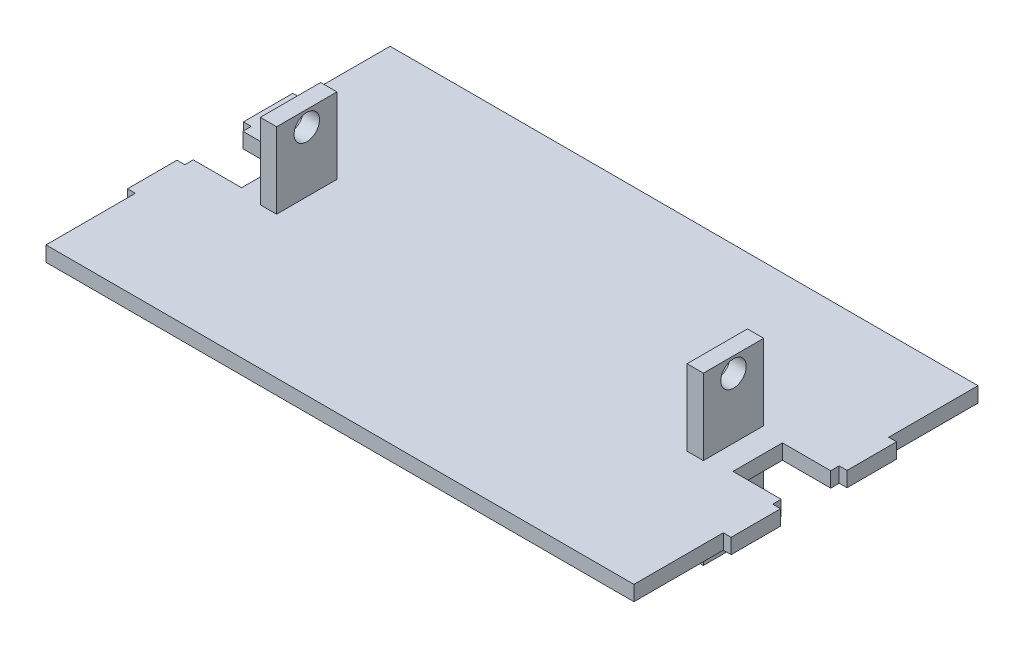
SolidWorks part; units mm, degrees
ref_plane "Front Plane" through (0, 0, 0) normal (0, 0, 1) x (1, 0, 0)
ref_plane "Top Plane" through (0, 0, 0) normal (0, 1, 0) x (1, 0, 0)
ref_plane "Right Plane" through (0, 0, 0) normal (1, 0, 0) x (0, 0, -1)
sketch "Sketch1" plane through (0, 0, 0) normal (0, 1, 0) x (1, 0, 0)
  line L0 (0, 72.39) -> (0, -72.39) construction
  line L1 (123.698, -72.39) -> (-123.698, -72.39)
  line L2 (123.698, -72.39) -> (123.698, -34.798)
  line L3 (123.698, 72.39) -> (-123.698, 72.39)
  line L4 (-123.698, -72.39) -> (-123.698, -34.798)
  line L5 (123.698, -72.39) -> (-123.698, 72.39) construction
  line L6 (123.698, 72.39) -> (-123.698, -72.39) construction
  line L7 (123.698, 10.414) -> (103.378, 10.414)
  line L9 (123.698, -10.414) -> (103.378, -10.414)
  line L10 (103.378, 10.414) -> (103.378, -10.414)
  line L13 (-123.698, -10.414) -> (-103.378, -10.414)
  line L14 (-103.378, 10.414) -> (-103.378, -10.414)
  line L15 (-123.698, 10.414) -> (-103.378, 10.414)
  line L17 (-126.9885, 0) -> (127.0115, 0) construction
  line L18 (-123.698, 13.97) -> (-127, 13.97)
  line L20 (-123.698, 34.798) -> (-127, 34.798)
  line L21 (-127, 13.97) -> (-127, 34.798)
  line L22 (-123.698, -34.798) -> (-127, -34.798)
  line L23 (-127, -13.97) -> (-127, -34.798)
  line L24 (-123.698, -13.97) -> (-127, -13.97)
  line L27 (123.698, -13.97) -> (127, -13.97)
  line L28 (127, -13.97) -> (127, -34.798)
  line L29 (123.698, -34.798) -> (127, -34.798)
  line L30 (123.698, 34.798) -> (127, 34.798)
  line L31 (127, 13.97) -> (127, 34.798)
  line L32 (123.698, 13.97) -> (127, 13.97)
  line L34 (-123.698, 34.798) -> (-123.698, 72.39)
  line L35 (-123.698, -13.97) -> (-123.698, -10.414)
  line L36 (123.698, 34.798) -> (123.698, 72.39)
  line L37 (123.698, -13.97) -> (123.698, -10.414)
  line L38 (-123.698, 10.414) -> (-123.698, 13.97)
  line L39 (123.698, 10.414) -> (123.698, 13.97)
  point P0 (0, 0)
  point P6 (127, 0)
  dimension "D1" = 247.396
  dimension "D2" = 144.78
  dimension "D3" = 20.828
  dimension "D5" = 3.302
  dimension "D6" = 20.828
  dimension "D4" = 20.32
  dimension "D7" = 3.556
  dimension "D8" = 3.556
  dimension "D9" = 3.556
  dimension "D10" = 3.556
  dimension "D11" = 37.592
  dimension "D12" = 20.828
  dimension "D13" = 37.592
extrude "Boss-Extrude1" add sketch "Sketch1" along normal mid plane 6.35
sketch "Sketch2" plane through (0, 0, 0) normal (0, 1, 0) x (1, 0, 0)
  line L0 (-103.378, 10.414) -> (-103.378, -10.414) construction
  line L1 (86.36, -12.7) -> (93.218, -12.7)
  line L2 (86.36, -12.7) -> (86.36, 12.7)
  line L3 (86.36, 12.7) -> (93.218, 12.7)
  line L4 (93.218, -12.7) -> (93.218, 12.7)
  line L5 (86.36, -12.7) -> (93.218, 12.7) construction
  line L6 (86.36, 12.7) -> (93.218, -12.7) construction
  line L9 (-86.36, -12.7) -> (-86.36, 12.7)
  line L10 (-86.36, 12.7) -> (-93.218, 12.7)
  line L11 (-93.218, -12.7) -> (-93.218, 12.7)
  line L12 (-86.36, -12.7) -> (-93.218, -12.7)
  line L13 (103.378, -10.414) -> (103.378, 10.414) construction
  point P0 (89.789, 0)
  point P10 (103.378, 0)
  dimension "D1" = 10.16
  dimension "D2" = 10.16
  dimension "D3" = 25.4
  dimension "D4" = 25.4
  dimension "D5" = 6.858
  dimension "D6" = 6.858
  dimension "D7" = 6.858
extrude "Boss-Extrude2" add sketch "Sketch2" along normal mid plane 70.104
sketch "Sketch3" plane through (-93.218, 0, 0) normal (-1, 0, 0) x (0, 0, 1)
  line L0 (12.7, 3.175) -> (-12.7, 3.175) construction
  line L1 (12.7, -3.175) -> (-12.7, -3.175) construction
  circle A0 centre (0, 28.575) radius 5.3578
  circle A1 centre (0, -28.575) radius 5.3578
  dimension "D1" = 10.7156
  dimension "D2" = 10.7156
  dimension "D3" = 25.4
  dimension "D4" = 25.4
extrude "Cut-Extrude1" cut sketch "Sketch3" against normal through all both and the other way through all
equation "\"length\"=9.74"
equation "\"width\"=5.7"
equation "\"height\"= 0.25"
equation "\"D1@Sketch1\"=\"length\""
equation "\"D2@Sketch1\"=\"width\""
equation "\"eyebolt width\"= 0.82"
equation "\"eyebolt length\"= 0.8"
equation "\"D3@Sketch1\"=\"eyebolt width\""
equation "\"D4@Sketch1\"=\"eyebolt length\""
equation "\"lead screw holder height\"= 2.76"
equation "\"Lead_Screw_Diam\" = (27/64)*1in"
equation "\"D1@Sketch3\" = \"Lead_Screw_Diam\""
equation "\"distance from holders to board\"=0.4"
equation "\"D2@Sketch3\" = \"Lead_Screw_Diam\""
equation "\"Lead_Screw_Dist\" = 2.25in"
equation "\"D3@Sketch3\"=(\"Lead_Screw_Dist\"-\"height\")/2"
equation "\"D4@Sketch3\"=(\"Lead_Screw_Dist\"-\"height\")/2"
